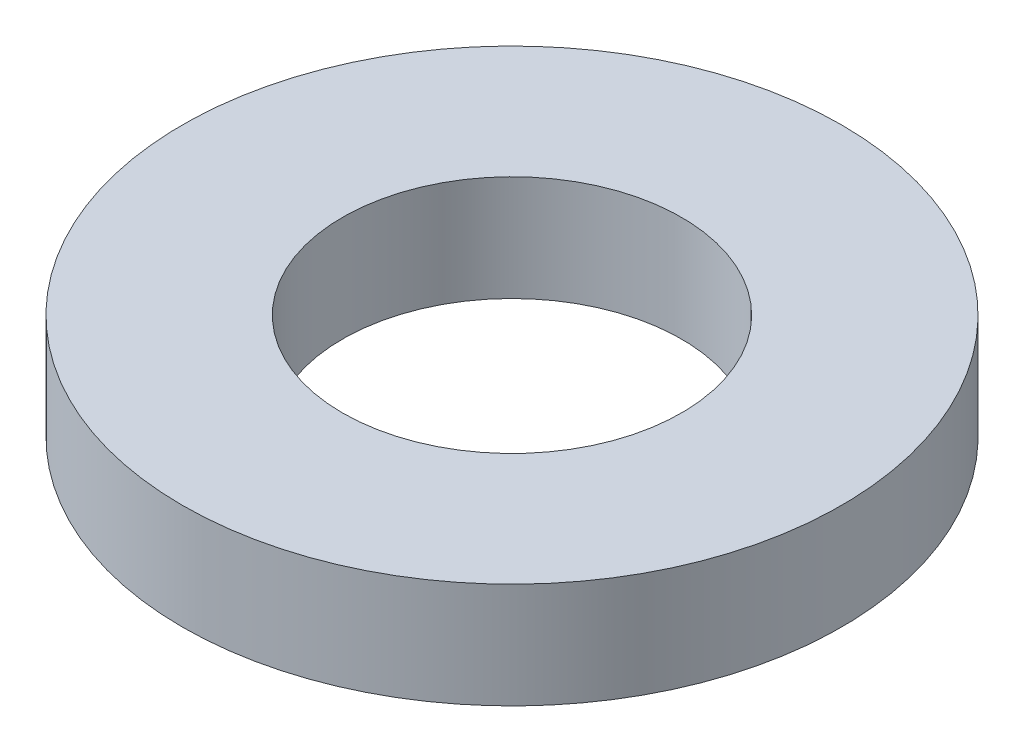
SolidWorks part; units mm, degrees
ref_plane "Front Plane" through (0, 0, 0) normal (0, 0, 1) x (1, 0, 0)
ref_plane "Top Plane" through (0, 0, 0) normal (0, 1, 0) x (1, 0, 0)
ref_plane "Right Plane" through (0, 0, 0) normal (1, 0, 0) x (0, 0, -1)
sketch "Sketch1" plane through (0, 0, 0) normal (0, 1, 0) x (1, 0, 0)
  circle A0 centre (0, 0) radius 87.5
  dimension "FLANGE_OD" = 175
extrude "Boss-Extrude1" add sketch "Sketch1" along normal blind 28
sketch "Sketch2" plane through (0, 0, 0) normal (0, 1, 0) x (1, 0, 0)
  circle A0 centre (0, 0) radius 45
  dimension "BORE_D" = 90
extrude "Cut-Extrude1" cut sketch "Sketch2" along normal through all
sketch "Sketch3" plane through (0, 28, 0) normal (0, 1, 0) x (1, 0, 0)
  circle A0 centre (0, 0) radius 26.4916 construction
  circle A1 centre (-26.4916, 0) radius 6.8932
  dimension "BOLT_D" = 13.7865
  dimension "BOLT_PCD" = 52.9832
extrude "Cut-Extrude2" cut sketch "Sketch3" against normal blind 23.9475 rebuild error yes
pattern_circular "CirPattern1" count 3 over 360 rebuild error yes
